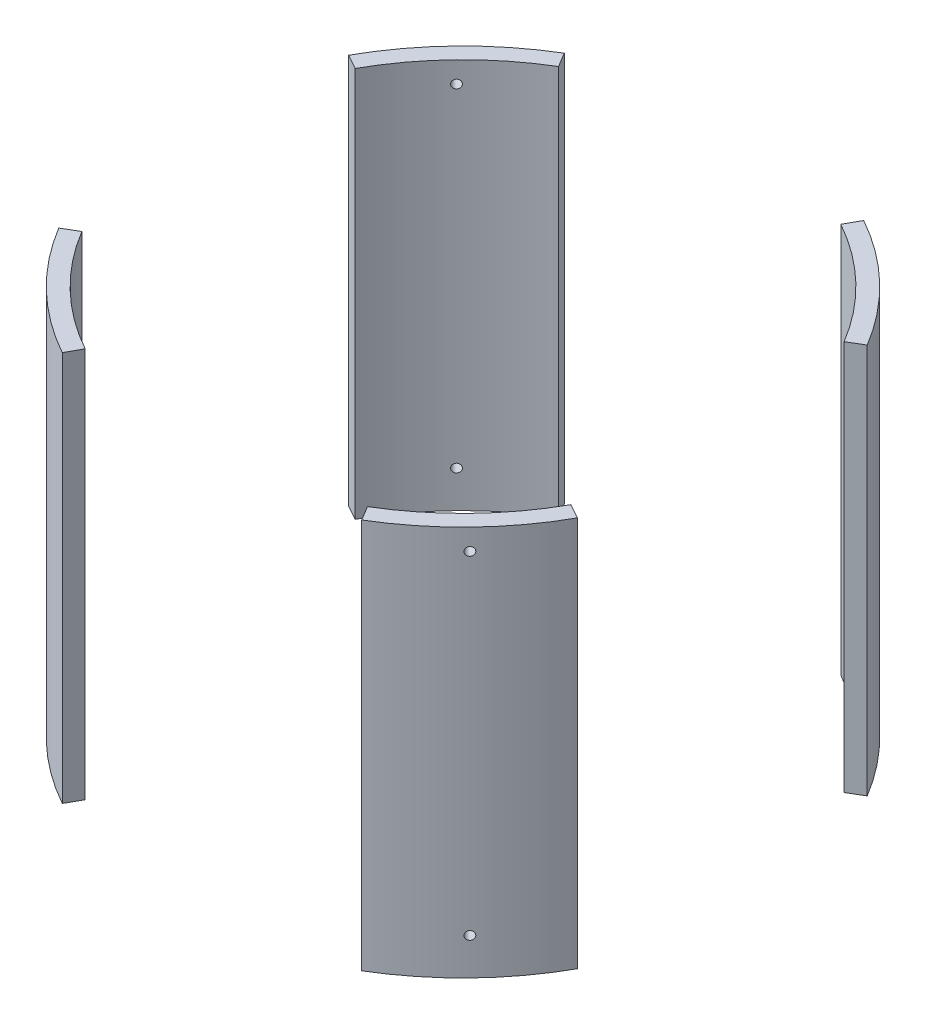
SolidWorks part; units mm, degrees
material "6061-T6 (SS)"
ref_plane "Front Plane" through (0, 0, 0) normal (0, 0, 1) x (1, 0, 0)
ref_plane "Top Plane" through (0, 0, 0) normal (0, 1, 0) x (1, 0, 0)
ref_plane "Right Plane" through (0, 0, 0) normal (1, 0, 0) x (0, 0, -1)
sketch "Sketch2" plane through (0, 0, 0) normal (0, 1, 0) x (1, 0, 0)
  circle A0 centre (0, 0) radius 88.9
  circle A1 centre (0, 0) radius 83.82
  dimension "D1" = 177.8
  dimension "D2" = 167.64
extrude "Boss-Extrude1" add sketch "Sketch2" along normal mid plane 117.8027
sketch "Sketch3" plane through (0, 0, 0) normal (0, 1, 0) x (1, 0, 0)
  line L0 (0, 0) -> (169.6618, 101.6776)
  line L1 (-58.1167, 96.9749) -> (0, 0)
  line L2 (0, 0) -> (53.9, 96.9749)
  line L3 (53.9, 96.9749) -> (-58.1167, 96.9749)
  line L4 (0, 0) -> (70.9917, -118.4586)
  line L5 (70.9917, -118.4586) -> (-65.8409, -118.4586)
  line L6 (-65.8409, -118.4586) -> (0, 0)
  line L7 (169.6618, 101.6776) -> (169.6618, -94.3004)
  line L8 (169.6618, -94.3004) -> (0, 0)
  line L9 (0, 0) -> (-123.7413, 68.7771)
  line L10 (-123.7413, 68.7771) -> (-123.7413, -74.1577)
  line L11 (-123.7413, -74.1577) -> (0, 0)
  dimension "D1" = 60
  dimension "D2" = 60
  dimension "D3" = 60
  dimension "D4" = 60
  dimension "D5" = 30
  dimension "D6" = 30
extrude "Cut-Extrude1" cut sketch "Sketch3" against normal through all both and the other way through all contours L8 L7 L0 | L2 L3 L1 | L10 L11 L9 | L6 L5 L4 region at (-1.4056, 0, -64.65) region at (1.7169, 0, 78.9724) region at (113.1078, 0, -2.4591) region at (-82.4942, 0, 1.7935)
ref_plane "Bolt reference plane" through (-56.3092, 0, 58.1758) normal (0.6955, 0, -0.7185) x (-0.7185, 0, -0.6955)
sketch "Sketch5" plane through (-56.3092, 0, 58.1758) normal (0.6955, 0, -0.7185) x (-0.7185, 0, -0.6955)
  line L0 (-23.009, -58.9013) -> (23.009, -58.9013) construction
  circle A0 centre (-0.0228, 52.5513) radius 1.27
  circle A1 centre (-0.0228, -47.7888) radius 1.27
  dimension "D1" = 2.54
  dimension "D4" = 11.1125
  dimension "D2" = 21.717
  dimension "D3" = 6.35
extrude "Bolt holes" cut sketch "Sketch5" against normal through all
pattern_circular "Bolt pattern" count 4 over 360 about axis through (0, 58.9013, 0) along (0, 1, 0) of "Bolt holes"
equation "\"D1@Boss-Extrude1\"=3*12"
